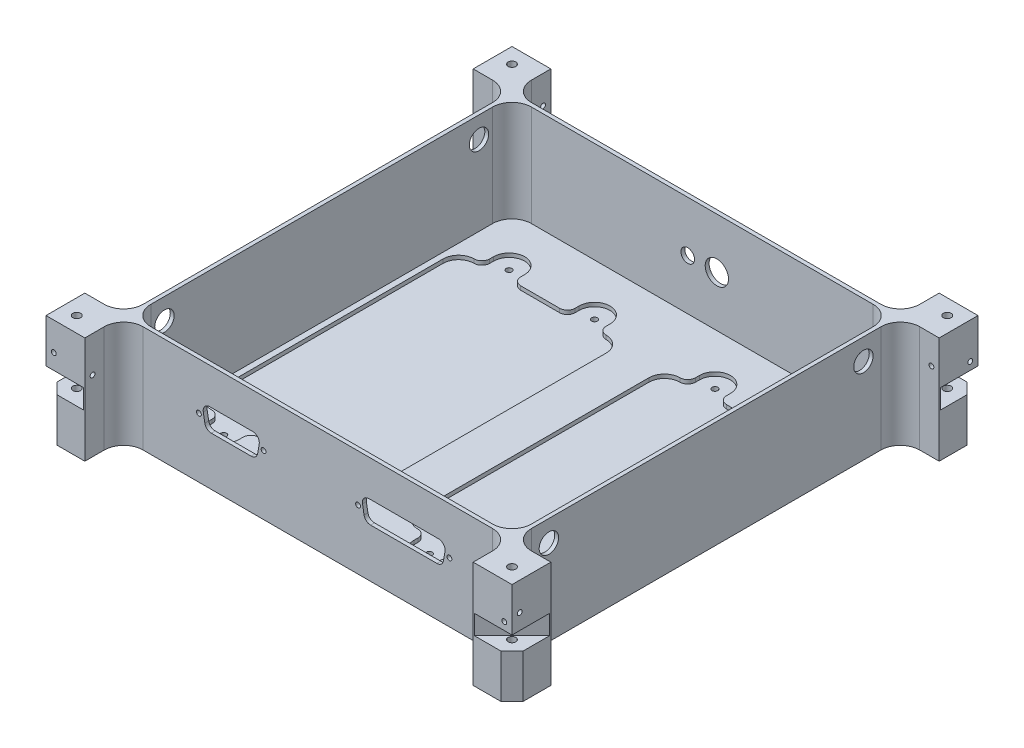
SolidWorks part; units mm, degrees
ref_plane "Front" through (0, 0, 0) normal (0, 0, 1) x (1, 0, 0)
ref_plane "Top" through (0, 0, 0) normal (0, 1, 0) x (1, 0, 0)
ref_plane "Right" through (0, 0, 0) normal (1, 0, 0) x (0, 0, -1)
sketch "Sketch1" plane through (0, 0, 0) normal (0, 1, 0) x (1, 0, 0)
  line L0 (0, 0) -> (0, -42.0956) construction
  line L1 (-120, 120) -> (120, 120)
  line L2 (-120, 120) -> (-120, -120)
  line L3 (-120, -120) -> (120, -120)
  line L4 (120, 120) -> (120, -120)
  line L5 (-120, -120) -> (-100, -120)
  line L6 (-120, -120) -> (-120, -100)
  line L7 (-120, -100) -> (-110, -100)
  line L8 (-100, -120) -> (-100, -110)
  line L9 (-120, 120) -> (-100, 120)
  line L10 (-120, 120) -> (-120, 100)
  line L11 (-120, 100) -> (-110, 100)
  line L12 (-100, 120) -> (-100, 110)
  line L13 (120, 120) -> (100, 120)
  line L14 (120, 120) -> (120, 100)
  line L15 (120, 100) -> (110, 100)
  line L16 (100, 120) -> (100, 110)
  line L17 (110, -100) -> (120, -100)
  line L18 (100, -110) -> (100, -120)
  line L19 (100, -120) -> (120, -120)
  line L20 (120, -100) -> (120, -120)
  line L21 (90, 100) -> (-90, 100)
  line L22 (100, 90) -> (100, -90)
  line L23 (90, -100) -> (-90, -100)
  line L24 (-100, 90) -> (-100, -90)
  line L25 (0, 0) -> (-45.3624, 0) construction
  arc A0 (-90, -100) -> (-100, -110) centre (-90, -110) ccw
  arc A1 (-110, -100) -> (-100, -90) centre (-110, -90) ccw
  arc A2 (110, -100) -> (100, -90) centre (110, -90) cw
  arc A3 (90, -100) -> (100, -110) centre (90, -110) cw
  arc A4 (110, 100) -> (100, 90) centre (110, 90) ccw
  arc A5 (90, 100) -> (100, 110) centre (90, 110) ccw
  arc A6 (-110, 100) -> (-100, 90) centre (-110, 90) cw
  arc A7 (-90, 100) -> (-100, 110) centre (-90, 110) cw
  dimension "D14" = 20
  dimension "D5" = 20
  dimension "D1" = 240
  dimension "D2" = 240
  dimension "D3" = 120
  dimension "D4" = 120
  dimension "D15" = 10
  dimension "D16" = 10
extrude "Boss-Extrude1" add sketch "Sketch1" along normal mid plane 55 contours L21 A7 L12 L1 L2 L11 A6 L24 A1 L7 L3 L8 A0 L23 A3 L18 L4 L17 A2 L22 A4 L15 L16 A5 region at (0, 0, 0)
sketch "Sketch2" plane through (0, 27.5, 0) normal (0, 1, 0) x (1, 0, 0)
  line L0 (90, 100) -> (-90, 100) construction
  line L1 (-88, 98) -> (88, 98)
  line L2 (-98, 88) -> (-98, -88)
  line L3 (-88, -98) -> (88, -98)
  line L4 (98, 88) -> (98, -88)
  line L5 (90, -100) -> (-90, -100) construction
  line L6 (100, 90) -> (100, -90) construction
  line L7 (-100, 90) -> (-100, -90) construction
  arc A0 (-98, -88) -> (-88, -98) centre (-88, -88) ccw
  arc A1 (88, -98) -> (98, -88) centre (88, -88) ccw
  arc A2 (88, 98) -> (98, 88) centre (88, 88) cw
  arc A3 (-88, 98) -> (-98, 88) centre (-88, 88) ccw
  dimension "D5" = 10
  dimension "D1" = 2
  dimension "D2" = 2
  dimension "D3" = 2
  dimension "D4" = 2
extrude "Cut-Extrude1" cut sketch "Sketch2" against normal blind 52
sketch "Sketch3" plane through (0, -24.5, 0) normal (0, 1, 0) x (1, 0, 0)
  line L0 (-98, 88) -> (-98, -88) construction
  line L1 (-95, 67.5) -> (-87, 67.5)
  line L2 (-95, 67.5) -> (-95, -67.5)
  line L3 (-95, -67.5) -> (-87, -67.5)
  line L4 (-11, 67.5) -> (-11, -67.5)
  line L5 (-120, -100) -> (-120, -120) construction
  line L6 (-120, -120) -> (-100, -120) construction
  line L7 (-23, -73.5) -> (-23, -71.5)
  line L8 (-39, -73.5) -> (-39, -71.5)
  line L9 (-67, -73.5) -> (-67, -71.5)
  line L10 (-83, -73.5) -> (-83, -71.5)
  line L11 (-63, -67.5) -> (-43, -67.5)
  line L12 (-19, -67.5) -> (-11, -67.5)
  line L13 (-88, -98) -> (88, -98) construction
  line L14 (0, 0) -> (-67, 0) construction
  line L15 (-19, 67.5) -> (-11, 67.5)
  line L16 (-63, 67.5) -> (-43, 67.5)
  line L17 (-83, 73.5) -> (-83, 71.5)
  line L18 (-67, 73.5) -> (-67, 71.5)
  line L19 (-39, 73.5) -> (-39, 71.5)
  line L20 (-23, 73.5) -> (-23, 71.5)
  line L21 (-95, 67.5) -> (-87, 67.5)
  line L22 (-63, 67.5) -> (-43, 67.5)
  line L23 (-19, 67.5) -> (-11, 67.5)
  line L24 (0, 0) -> (0, 64.5999) construction
  line L25 (19, 67.5) -> (11, 67.5)
  line L26 (19, 67.5) -> (11, 67.5)
  line L27 (63, 67.5) -> (43, 67.5)
  line L28 (95, 67.5) -> (87, 67.5)
  line L29 (23, 73.5) -> (23, 71.5)
  line L30 (39, 73.5) -> (39, 71.5)
  line L31 (67, 73.5) -> (67, 71.5)
  line L32 (83, 73.5) -> (83, 71.5)
  line L33 (63, 67.5) -> (43, 67.5)
  line L34 (19, -67.5) -> (11, -67.5)
  line L35 (63, -67.5) -> (43, -67.5)
  line L36 (83, -73.5) -> (83, -71.5)
  line L37 (67, -73.5) -> (67, -71.5)
  line L38 (39, -73.5) -> (39, -71.5)
  line L39 (23, -73.5) -> (23, -71.5)
  line L40 (11, 67.5) -> (11, -67.5)
  line L41 (95, -67.5) -> (87, -67.5)
  line L42 (95, 67.5) -> (95, -67.5)
  line L43 (95, 67.5) -> (87, 67.5)
  arc A0 (-83, -73.5) -> (-67, -73.5) centre (-75, -73.5) ccw
  arc A1 (-39, -73.5) -> (-23, -73.5) centre (-31, -73.5) ccw
  arc A2 (-83, -71.5) -> (-87, -67.5) centre (-87, -71.5) ccw
  arc A3 (-63, -67.5) -> (-67, -71.5) centre (-63, -71.5) ccw
  arc A4 (-39, -71.5) -> (-43, -67.5) centre (-43, -71.5) ccw
  arc A5 (-19, -67.5) -> (-23, -71.5) centre (-19, -71.5) ccw
  arc A6 (-19, 67.5) -> (-23, 71.5) centre (-19, 71.5) cw
  arc A7 (-39, 71.5) -> (-43, 67.5) centre (-43, 71.5) cw
  arc A8 (-63, 67.5) -> (-67, 71.5) centre (-63, 71.5) cw
  arc A9 (-83, 71.5) -> (-87, 67.5) centre (-87, 71.5) cw
  arc A10 (-39, 73.5) -> (-23, 73.5) centre (-31, 73.5) cw
  arc A11 (-83, 73.5) -> (-67, 73.5) centre (-75, 73.5) cw
  circle A12 centre (-75, 73.5) radius 1.5
  circle A13 centre (-31, 73.5) radius 1.5
  circle A14 centre (-31, -73.5) radius 1.5
  circle A15 centre (-75, -73.5) radius 1.5
  arc A16 (-87, 67.5) -> (-95, 59.5) centre (-87, 59.5) ccw
  arc A17 (-11, 59.5) -> (-19, 67.5) centre (-19, 59.5) ccw
  arc A18 (-19, -67.5) -> (-11, -59.5) centre (-19, -59.5) ccw
  arc A19 (-95, -59.5) -> (-87, -67.5) centre (-87, -59.5) ccw
  arc A20 (95, -59.5) -> (87, -67.5) centre (87, -59.5) cw
  arc A21 (19, -67.5) -> (11, -59.5) centre (19, -59.5) cw
  arc A22 (11, 59.5) -> (19, 67.5) centre (19, 59.5) cw
  arc A23 (87, 67.5) -> (95, 59.5) centre (87, 59.5) cw
  circle A24 centre (75, -73.5) radius 1.5
  circle A25 centre (31, -73.5) radius 1.5
  circle A26 centre (31, 73.5) radius 1.5
  circle A27 centre (75, 73.5) radius 1.5
  arc A28 (83, 73.5) -> (67, 73.5) centre (75, 73.5) ccw
  arc A29 (39, 73.5) -> (23, 73.5) centre (31, 73.5) ccw
  arc A30 (83, 71.5) -> (87, 67.5) centre (87, 71.5) ccw
  arc A31 (63, 67.5) -> (67, 71.5) centre (63, 71.5) ccw
  arc A32 (39, 71.5) -> (43, 67.5) centre (43, 71.5) ccw
  arc A33 (19, 67.5) -> (23, 71.5) centre (19, 71.5) ccw
  arc A34 (19, -67.5) -> (23, -71.5) centre (19, -71.5) cw
  arc A35 (39, -71.5) -> (43, -67.5) centre (43, -71.5) cw
  arc A36 (63, -67.5) -> (67, -71.5) centre (63, -71.5) cw
  arc A37 (83, -71.5) -> (87, -67.5) centre (87, -71.5) cw
  arc A38 (39, -73.5) -> (23, -73.5) centre (31, -73.5) cw
  arc A39 (83, -73.5) -> (67, -73.5) centre (75, -73.5) cw
  dimension "D7" = 16
  dimension "D8" = 16
  dimension "D10" = 8
  dimension "D11" = 8
  dimension "D12" = 8
  dimension "D13" = 4
  dimension "D14" = 4
  dimension "D15" = 8
  dimension "D16" = 4
  dimension "D17" = 4
  dimension "D4" = 3
  dimension "D19" = 3
  dimension "D20" = 3
  dimension "D21" = 3
  dimension "D22" = 16
  dimension "D23" = 16
  dimension "D24" = 16
  dimension "D25" = 8
  dimension "D1" = 84
  dimension "D2" = 135
  dimension "D3" = 3
  dimension "D5" = 45
  dimension "D6" = 89
  dimension "D9" = 46.5
  dimension "D18" = 26.5
extrude "Cut-Extrude2" cut sketch "Sketch3" against normal blind 2 contours L2 A19 A2 L10 A0 L9 A3 L11 A4 L8 A1 L7 A5 A18 L4 A17 A6 L20 A10 L19 A7 L16 A8 L18 A11 L17 A9 A16 A15 A14 A13 A12 | A39 L36 A37 A20 L42 A23 A30 L32 A28 L31 A31 L27 A32 L30 A29 L29 A33 A22 L40 A21 A34 L39 A38 L38 A35 L35 A36 L37 A26 A24 A25 A27 region at (-53, -24.5, 0) region at (53, -24.5, 0)
sketch "Sketch5" plane through (0, -27.5, 0) normal (0, -1, 0) x (1, 0, 0)
  line L0 (90, 100) -> (-90, 100) construction
  line L1 (-88, 98) -> (88, 98)
  line L2 (-98, 88) -> (-98, -88)
  line L3 (-88, -98) -> (88, -98)
  line L4 (98, 88) -> (98, -88)
  line L5 (-100, -90) -> (-100, 90) construction
  line L6 (90, -100) -> (-90, -100) construction
  line L7 (100, -90) -> (100, 90) construction
  arc A3 (-98, -88) -> (-88, -98) centre (-88, -88) ccw
  arc A4 (88, -98) -> (98, -88) centre (88, -88) ccw
  arc A5 (88, 98) -> (98, 88) centre (88, 88) cw
  arc A6 (-88, 98) -> (-98, 88) centre (-88, 88) ccw
  dimension "D5" = 10
  dimension "D1" = 2
  dimension "D2" = 2
  dimension "D3" = 2
  dimension "D4" = 2
extrude "Boss-Extrude2" add sketch "Sketch5" along normal blind 2
extrude "Cut-Extrude3" cut sketch "Sketch3<3>" against normal up to next contours A12 | A13 | A26 | A27 | A15 | A14 | A25 | A24
sketch "Sketch3<3>" plane through (0, -24.5, 0) normal (0, 1, 0) x (1, 0, 0) same geometry as "Sketch3"
sketch "Sketch4" plane through (0, -29.5, 0) normal (0, -1, 0) x (1, 0, 0)
  line L0 (-20.1726, 75.4412) -> (-20.1453, 75.4428)
  line L1 (-88, 98) -> (88, 98)
  line L2 (-98, 88) -> (-98, -88)
  line L3 (-88, -98) -> (88, -98)
  line L4 (98, 88) -> (98, -88)
  line L5 (-100, -90) -> (-100, 90) construction
  line L6 (90, -100) -> (-90, -100) construction
  line L7 (-95, 88) -> (-95, 83.1437)
  line L8 (95, -88) -> (95, -83.1437)
  line L9 (95, 88) -> (95, 83.1437)
  line L10 (20.1453, 75.4428) -> (20.1726, 75.4412)
  line L11 (-58.2668, 70.5) -> (-47.7332, 70.5)
  line L12 (58.2668, -70.5) -> (47.7332, -70.5)
  line L13 (-20.1726, -75.4412) -> (-20.1453, -75.4428)
  line L14 (8, -59.5) -> (8, 59.5)
  line L15 (98, -70.5) -> (98, 70.5)
  line L17 (58.2668, 70.5) -> (47.7332, 70.5)
  line L18 (20.1726, -75.4412) -> (20.1453, -75.4428)
  line L21 (-98, -70.5) -> (-95, -70.5)
  line L22 (-98, -70.5) -> (-98, 70.5)
  line L23 (98, 88) -> (98, -88)
  line L24 (-8, -59.5) -> (-8, 59.5)
  line L25 (-95, -59.5) -> (-95, 59.5) construction
  line L27 (-63, -67.5) -> (-43, -67.5) construction
  line L29 (-58.2668, -70.5) -> (-47.7332, -70.5)
  line L30 (62.7139, 0) -> (-62.7139, 0) construction
  line L31 (0, 0) -> (0, 40.1064) construction
  line L32 (-88, 95) -> (88, 95)
  line L33 (-88, -95) -> (88, -95)
  line L34 (-95, 88) -> (-95, 83.1437)
  line L37 (-95, -88) -> (-95, -83.1437)
  arc A0 (-84.0588, -79.74) -> (-64.1726, -75.4412) centre (-75, -73.5) ccw
  arc A1 (-88, 98) -> (-98, 88) centre (-88, 88) ccw
  arc A2 (88, 98) -> (98, 88) centre (88, 88) cw
  arc A3 (88, -98) -> (98, -88) centre (88, -88) ccw
  arc A4 (-98, -88) -> (-88, -98) centre (-88, -88) ccw
  arc A5 (-15.8654, -70.0439) -> (-20.1453, -75.4428) centre (-14.1556, -75.7952) ccw
  arc A6 (84.0588, -79.74) -> (95, -83.1437) centre (89, -83.1437) cw
  arc A7 (-41.8274, 75.4412) -> (-47.7332, 70.5) centre (-47.7332, 76.5) cw
  arc A8 (-58.2668, 70.5) -> (-64.1726, 75.4412) centre (-58.2668, 76.5) cw
  arc A9 (-41.8274, 75.4412) -> (-20.1726, 75.4412) centre (-31, 73.5) cw
  arc A10 (-84.0588, 79.74) -> (-64.1726, 75.4412) centre (-75, 73.5) cw
  arc A11 (20.1453, -75.4428) -> (15.8654, -70.0439) centre (14.1556, -75.7952) ccw
  arc A12 (84.0588, 79.74) -> (95, 83.1437) centre (89, 83.1437) ccw
  arc A13 (41.8274, -75.4412) -> (47.7332, -70.5) centre (47.7332, -76.5) cw
  arc A14 (58.2668, -70.5) -> (64.1726, -75.4412) centre (58.2668, -76.5) cw
  arc A15 (41.8274, -75.4412) -> (20.1726, -75.4412) centre (31, -73.5) cw
  arc A16 (84.0588, 79.74) -> (64.1726, 75.4412) centre (75, 73.5) ccw
  arc A17 (41.8274, 75.4412) -> (20.1726, 75.4412) centre (31, 73.5) ccw
  arc A18 (58.2668, 70.5) -> (64.1726, 75.4412) centre (58.2668, 76.5) ccw
  arc A19 (41.8274, 75.4412) -> (47.7332, 70.5) centre (47.7332, 76.5) ccw
  arc A20 (15.8654, 70.0439) -> (20.1453, 75.4428) centre (14.1556, 75.7952) ccw
  arc A21 (-41.8274, -75.4412) -> (-20.1726, -75.4412) centre (-31, -73.5) ccw
  arc A22 (-58.2668, -70.5) -> (-64.1726, -75.4412) centre (-58.2668, -76.5) ccw
  arc A23 (-41.8274, -75.4412) -> (-47.7332, -70.5) centre (-47.7332, -76.5) ccw
  arc A24 (-84.0588, -79.74) -> (-95, -83.1437) centre (-89, -83.1437) ccw
  arc A25 (-20.1453, 75.4428) -> (-15.8654, 70.0439) centre (-14.1556, 75.7952) ccw
  arc A27 (98, -88) -> (88, -98) centre (88, -88) cw
  arc A28 (84.0588, -79.74) -> (64.1726, -75.4412) centre (75, -73.5) cw
  arc A29 (88, 95) -> (95, 88) centre (88, 88) cw
  arc A30 (-88, 95) -> (-95, 88) centre (-88, 88) ccw
  arc A31 (-95, -88) -> (-88, -95) centre (-88, -88) ccw
  arc A32 (88, -95) -> (95, -88) centre (88, -88) ccw
  arc A33 (-84.0588, 79.74) -> (-95, 83.1437) centre (-89, 83.1437) cw
  arc A49 (-8, 59.5) -> (-19, 70.5) centre (-19, 59.5) ccw
  arc A50 (-8, 59.5) -> (-15.8654, 70.0439) centre (-19, 59.5) ccw
  arc A52 (19, 70.5) -> (8, 59.5) centre (19, 59.5) ccw
  arc A53 (15.8654, 70.0439) -> (8, 59.5) centre (19, 59.5) ccw
  arc A55 (-19, -70.5) -> (-8, -59.5) centre (-19, -59.5) ccw
  arc A56 (-15.8654, -70.0439) -> (-8, -59.5) centre (-19, -59.5) ccw
  arc A58 (8, -59.5) -> (19, -70.5) centre (19, -59.5) ccw
  arc A59 (8, -59.5) -> (15.8654, -70.0439) centre (19, -59.5) ccw
  dimension "D5" = 10
  dimension "D10" = 22
  dimension "D11" = 22
  dimension "D12" = 12
  dimension "D13" = 12
  dimension "D14" = 90
  dimension "D15" = 12
  dimension "D8" = 12
  dimension "D16" = 3
  dimension "D20" = 12
  dimension "D6" = 12
  dimension "D21" = 12
  dimension "D2" = 2
  dimension "D3" = 2
  dimension "D4" = 3
  dimension "D7" = 3
  dimension "D9" = 3
  dimension "D17" = 3
  dimension "D18" = 3
  dimension "D19" = 3
extrude "Cut-Extrude4" cut sketch "Sketch4" against normal blind 2 contours A59 L14 A53 A20 L10 A17 A19 L17 A18 A16 A12 L9 A29 L32 A30 L7 A33 A10 A8 L11 A7 A9 L0 A25 A50 L24 A56 A5 L13 A21 A23 L29 A22 A0 A24 L37 A31 L33 A32 L8 A6 A28 A14 L12 A13 A15 L18 A11 region at (0, -29.5, 0)
sketch "Sketch6" plane through (0, -24.5, 0) normal (0, 1, 0) x (1, 0, 0)
  line L0 (-120, -120) -> (-100, -120) construction
  line L1 (100, -120) -> (120, -120) construction
  line L2 (-120, -100) -> (-120, -120) construction
  line L3 (120, -100) -> (120, -120) construction
  point P0 (-88, -81)
  point P1 (0, -81)
  point P2 (88, -81)
  dimension "D1" = 39
  dimension "D2" = 39
  dimension "D3" = 39
  dimension "D4" = 32
  dimension "D5" = 32
  dimension "D6" = 0
hole_wizard "Ø3.0 (3) Diameter Hole1" positions "Sketch8" profile "Sketch7" hole size "Ø3.0" standard "AS" end condition up to next
sketch "Sketch8" plane through (0, -24.5, 0) normal (0, 1, 0) x (1, 0, 0)
  point P0 (-88, -81)
  point P3 (0, -81)
  point P6 (88, -81)
sketch "Sketch7" plane through (-88, -24.5, 81) normal (1, 0, 0) x (0, 0, 1)
  line L0 (0, 0) -> (0, 3)
  line L1 (0, 3) -> (1.5, 3)
  line L2 (1.5, 3) -> (1.5, 0)
  line L5 (1.5, 0) -> (0, 0)
  line L11 (0, -6.35) -> (0, 107.95) construction
  dimension "Thru Hole Dia." = 3
  dimension "Thru Hole Depth" = 3
sketch "Sketch9" plane through (100, 0, 0) normal (1, 0, 0) x (0, 0, -1)
  line L0 (0, 0) -> (-20.7242, 0) construction
  line L1 (0, 0) -> (0, 15.0037) construction
  line L3 (-120, 27.5) -> (-120, -27.5) construction
  line L4 (-100, 27.5) -> (-120, 27.5) construction
  line L5 (90, 27.5) -> (-90, 27.5) construction
  point P0 (-81, 16.5)
  point P1 (-116, 13)
  point P10 (81, 16.5)
  point P11 (116, 13)
  dimension "D1" = 11
  dimension "D2" = 81
  dimension "D3" = 4
  dimension "D4" = 14.5
hole_wizard "Ø10.0 (10) Diameter Hole1" positions "Sketch14" profile "Sketch15" hole size "Ø10.0" standard "AS" end condition through all
sketch "Sketch14" plane through (100, 0, 0) normal (1, 0, 0) x (0, 0, -1)
  point P0 (-81, 16.5)
  point P3 (81, 16.5)
sketch "Sketch15" plane through (100, 16.5, 81) normal (0, 1, 0) x (0, 0, -1)
  line L0 (0, 0) -> (0, 220)
  line L1 (0, 220) -> (5, 220)
  line L2 (5, 220) -> (5, 0)
  line L5 (5, 0) -> (0, 0)
  line L11 (0, -6.35) -> (0, 107.95) construction
  dimension "Thru Hole Dia." = 10
  dimension "Thru Hole Depth" = 220
sketch "Sketch16" plane through (0, -27.5, 0) normal (0, -1, 0) x (1, 0, 0)
  line L0 (-120, -100.6111) -> (-100.6111, -120)
  line L1 (-120, -120) -> (-120, -100) construction
  line L2 (-120, -120) -> (-100, -120) construction
  line L3 (-100, -120) -> (-120, -100)
  line L4 (-120, -114.3431) -> (-114.3431, -120)
  line L5 (-120, -114.3431) -> (-120, -120)
  line L6 (-120, -120) -> (-114.3431, -120)
  line M25 (-120, -100) -> (-120, -120)
  line M26 (-120, -120) -> (-100, -120)
  dimension "D1" = 13.71
  dimension "D2" = 4
extrude "Cut-Extrude5" cut sketch "Sketch16" against normal blind 22.5 contours L4 M25 M26 region at (-118.1144, -27.5, -118.1144)
ref_axis "Axis1" through (0, 0, 0) along (0, 1, 0)
pattern_circular "CirPattern1" count 4 over 360 about axis through (0, 0, 0) along (0, 1, 0) of "Cut-Extrude5"
ref_plane "Plane1" through (0, -5, 0) normal (0, -1, 0) x (-1, 0, 0)
sketch "Sketch17" plane through (0, -5, 0) normal (0, -1, 0) x (-1, 0, 0)
  line L0 (-114.3431, 120) -> (-120, 120)
  line L1 (-120, 120) -> (-120, 114.3431)
  line L2 (-120, 100.6111) -> (-100.6111, 120)
  line L3 (-120, 114.3431) -> (-120, 100) construction
  line L4 (-100, 120) -> (-114.3431, 120) construction
  line L5 (-120, 100) -> (-110, 100) construction
  line L6 (-120, 114.3431) -> (-120, 100.6111)
  line L7 (-114.3431, 120) -> (-100.6111, 120)
  dimension "D1" = 13.71
  dimension "D2" = 45
extrude "Cut-Extrude6" cut sketch "Sketch17" against normal blind 10
pattern_circular "CirPattern2" count 4 over 360 about axis through (0, 0, 0) along (0, 1, 0) of "Cut-Extrude6"
sketch "Sketch18" plane through (0, 0, -100) normal (0, 0, -1) x (-1, 0, 0)
  line L0 (-23.4875, 0) -> (26.2507, 0) construction
  line L1 (0, 0) -> (0, 15.8284) construction
  circle A0 centre (-7.5, 1.5) radius 6
  circle A1 centre (7.5, 1.5) radius 3.5
  dimension "D5" = 12
  dimension "D6" = 7
  dimension "D1" = 7.5
  dimension "D2" = 7.5
  dimension "D3" = 1.5
  dimension "D4" = 1.5
extrude "Cut-Extrude7" cut sketch "Sketch18" against normal up to next
sketch "Sketch19" plane through (0, 0, -120) normal (0, 0, -1) x (-1, 0, 0)
  line L0 (-120, 27.5) -> (-120, 5) construction
  line L2 (-100, 27.5) -> (-120, 27.5) construction
  line L3 (120, 27.5) -> (120, 5) construction
  line L4 (120, 27.5) -> (100, 27.5) construction
  point P0 (-116, 13)
  point P1 (116, 13)
  dimension "D1" = 4
  dimension "D2" = 14.5
  dimension "D3" = 4
  dimension "D4" = 14.5
sketch "Sketch22" plane through (0, 27.5, 0) normal (0, 1, 0) x (1, 0, 0)
  line L0 (-120, 100.6111) -> (-100.6111, 120)
  line L1 (-120, 120) -> (-120, 100) construction
  line L2 (-120, 120) -> (-100, 120) construction
  line L3 (-120, 100) -> (-110, 100) construction
  line L4 (0, 0) -> (-112.0764, 112.0764) construction
  line L5 (0, 0) -> (48.7369, 0) construction
  circle A0 centre (-112.0764, 112.0764) radius 2
  dimension "D4" = 4
  dimension "D1" = 13.71
  dimension "D2" = 45
  dimension "D3" = 158.5
  dimension "D5" = 135
extrude "Cut-Extrude8" cut sketch "Sketch22" against normal through all contours A0 region at (-112.0764, 27.5, -112.0764)
pattern_circular "CirPattern3" count 4 every 90 about axis through (0, 0, 0) along (0, 1, 0) of "Cut-Extrude8"
hole_wizard "M3x0.5 Tapped Hole1" positions "Sketch24" profile "Sketch23" tap size "M3x0.5" standard "ANSI Metric"
sketch "Sketch24" plane through (-120, 0, 0) normal (-1, 0, 0) x (0, 0, 1)
  line L0 (100, 27.5) -> (120, 27.5) construction
  line L1 (120, 27.5) -> (120, 5) construction
  line L2 (-120, 27.5) -> (-100, 27.5) construction
  line L3 (-120, 27.5) -> (-120, 5) construction
  point P0 (-116, 13)
  point P2 (116, 9)
  dimension "D1" = 18.5
  dimension "D2" = 4
  dimension "D3" = 14.5
  dimension "D4" = 4
sketch "Sketch23" plane through (-120, 13, -116) normal (0, 1, 0) x (0, 0, 1)
  line L0 (0, 0) -> (0, 20.7511)
  line L1 (0, 20.7511) -> (1.25, 20)
  line L2 (1.25, 20) -> (1.25, 0)
  line L5 (1.25, 0) -> (0, 0)
  line L10 (0, 20.7511) -> (-1.25, 20) construction
  line L11 (0, -6.35) -> (0, 107.95) construction
  dimension "Tap Drill Dia." = 2.5
  dimension "Tap Drill Depth" = 20
  dimension "Drill Angle" = 118
cosmetic thread "Hole Thread1" parameters "D1"=20, "D2"=4
cosmetic thread "Hole Thread2" parameters "D1"=20, "D2"=4
hole_wizard "M3x0.5 Tapped Hole2" positions "Sketch26" profile "Sketch25" tap size "M3x0.5" standard "ANSI Metric"
sketch "Sketch26" plane through (0, 0, 120) normal (0, 0, 1) x (1, 0, 0)
  line L0 (-120, 27.5) -> (-100, 27.5) construction
  line L1 (-120, 27.5) -> (-120, 5) construction
  line L2 (100, 27.5) -> (120, 27.5) construction
  line L4 (120, 27.5) -> (120, 5) construction
  point P0 (-116, 13)
  point P2 (116, 9)
  dimension "D1" = 14.5
  dimension "D2" = 4
  dimension "D3" = 18.5
  dimension "D4" = 4
sketch "Sketch25" plane through (-116, 13, 120) normal (1, 0, 0) x (0, -1, 0)
  line L0 (0, 0) -> (0, 22.2511)
  line L1 (0, 22.2511) -> (1.25, 21.5)
  line L2 (1.25, 21.5) -> (1.25, 0)
  line L5 (1.25, 0) -> (0, 0)
  line L10 (0, 22.2511) -> (-1.25, 21.5) construction
  line L11 (0, -6.35) -> (0, 107.95) construction
  dimension "Tap Drill Dia." = 2.5
  dimension "Tap Drill Depth" = 21.5
  dimension "Drill Angle" = 118
cosmetic thread "Hole Thread3" parameters "D1"=20, "D2"=3
cosmetic thread "Hole Thread4" parameters "D1"=20, "D2"=3
hole_wizard "M3x0.5 Tapped Hole3" positions "Sketch28" profile "Sketch27" tap size "M3x0.5" standard "ANSI Metric"
sketch "Sketch28" plane through (120, 0, 0) normal (1, 0, 0) x (0, 0, -1)
  line L0 (-100, 27.5) -> (-120, 27.5) construction
  line L1 (-120, 27.5) -> (-120, 5) construction
  line L2 (120, 27.5) -> (100, 27.5) construction
  line L3 (120, 27.5) -> (120, 5) construction
  point P0 (-116, 13)
  point P2 (116, 9)
  dimension "D1" = 14.5
  dimension "D2" = 4
  dimension "D3" = 18.5
  dimension "D4" = 4
sketch "Sketch27" plane through (120, 13, 116) normal (0, 1, 0) x (0, 0, -1)
  line L0 (0, 0) -> (0, 22.2511)
  line L1 (0, 22.2511) -> (1.25, 21.5)
  line L2 (1.25, 21.5) -> (1.25, 0)
  line L5 (1.25, 0) -> (0, 0)
  line L10 (0, 22.2511) -> (-1.25, 21.5) construction
  line L11 (0, -6.35) -> (0, 107.95) construction
  dimension "Tap Drill Dia." = 2.5
  dimension "Tap Drill Depth" = 21.5
  dimension "Drill Angle" = 118
cosmetic thread "Hole Thread5" parameters "D1"=20, "D2"=3
cosmetic thread "Hole Thread6" parameters "D1"=20, "D2"=3
hole_wizard "M3x0.5 Tapped Hole4" positions "Sketch30" profile "Sketch29" tap size "M3x0.5" standard "ANSI Metric"
sketch "Sketch30" plane through (0, 0, -120) normal (0, 0, -1) x (-1, 0, 0)
  line L0 (120, 27.5) -> (120, 5) construction
  line L1 (120, 27.5) -> (100, 27.5) construction
  line L2 (-120, 27.5) -> (-120, 5) construction
  line L3 (-100, 27.5) -> (-120, 27.5) construction
  point P0 (-116, 13)
  point P2 (116, 9)
  dimension "D1" = 4
  dimension "D2" = 18.5
  dimension "D3" = 4
  dimension "D4" = 14.5
sketch "Sketch29" plane through (116, 13, -120) normal (1, 0, 0) x (0, 1, 0)
  line L0 (0, 0) -> (0, 22.2511)
  line L1 (0, 22.2511) -> (1.25, 21.5)
  line L2 (1.25, 21.5) -> (1.25, 0)
  line L5 (1.25, 0) -> (0, 0)
  line L10 (0, 22.2511) -> (-1.25, 21.5) construction
  line L11 (0, -6.35) -> (0, 107.95) construction
  dimension "Tap Drill Dia." = 2.5
  dimension "Tap Drill Depth" = 21.5
  dimension "Drill Angle" = 118
cosmetic thread "Hole Thread7" parameters "D1"=20, "D2"=3
cosmetic thread "Hole Thread8" parameters "D1"=20, "D2"=3
sketch "Sketch31" plane through (0, 0, 100) normal (0, 0, 1) x (1, 0, 0)
  line L0 (-55.6517, 9) -> (-33.5483, 9)
  line L1 (-59, 5.0096) -> (-58.1889, 0.4096)
  line L2 (-30.2, 5.0096) -> (-31.0111, 0.4096)
  line L3 (-34.3595, -2.4) -> (-54.8405, -2.4)
  line L4 (90, 27.5) -> (-90, 27.5) construction
  line L6 (26.3483, 9) -> (62.1517, 9)
  line L7 (65.5, 5.0096) -> (64.6889, 0.4096)
  line L8 (61.3405, -2.4) -> (27.1595, -2.4)
  line L9 (23.8111, 0.4096) -> (23, 5.0096)
  line L12 (120, 27.5) -> (120, 5) construction
  line L13 (-120, 27.5) -> (-120, 5) construction
  arc A0 (-33.5483, 9) -> (-30.2, 5.0096) centre (-33.5483, 5.6) cw
  arc A1 (-55.6517, 9) -> (-59, 5.0096) centre (-55.6517, 5.6) ccw
  arc A2 (-31.0111, 0.4096) -> (-34.3595, -2.4) centre (-34.3595, 1) cw
  arc A3 (-58.1889, 0.4096) -> (-54.8405, -2.4) centre (-54.8405, 1) ccw
  arc A4 (62.1517, 9) -> (65.5, 5.0096) centre (62.1517, 5.6) cw
  arc A5 (64.6889, 0.4096) -> (61.3405, -2.4) centre (61.3405, 1) cw
  arc A6 (27.1595, -2.4) -> (23.8111, 0.4096) centre (27.1595, 1) cw
  arc A7 (23, 5.0096) -> (26.3483, 9) centre (26.3483, 5.6) cw
  dimension "D1" = 3.4
  dimension "D2" = 3.4
  dimension "D3" = 3.4
  dimension "D4" = 3.4
  dimension "D11" = 3.4
  dimension "D12" = 3.4
  dimension "D13" = 3.4
  dimension "D14" = 3.4
  dimension "D19" = 61
  dimension "D5" = 11.4
  dimension "D6" = 28.8
  dimension "D7" = 80
  dimension "D8" = 80
  dimension "D9" = 18.5
  dimension "D10" = 54.5
  dimension "D15" = 42.5
  dimension "D16" = 11.4
  dimension "D17" = 80
  dimension "D18" = 80
extrude "Cut-Extrude9" cut sketch "Sketch31" against normal blind 10
hole_wizard "M3x0.5 Tapped Hole5" positions "Sketch33" profile "Sketch32" tap size "M3x0.5" standard "ANSI Metric"
sketch "Sketch33" plane through (0, 0, 100) normal (0, 0, 1) x (1, 0, 0)
  line L0 (-54.8405, -2.4) -> (-34.3595, -2.4) construction
  line L2 (62.1517, 9) -> (26.3483, 9) construction
  arc A0 (-55.6517, 9) -> (-59, 5.0096) centre (-55.6517, 5.6) ccw construction
  arc A2 (-30.2, 5.0096) -> (-33.5483, 9) centre (-33.5483, 5.6) ccw construction
  arc A3 (26.3483, 9) -> (23, 5.0096) centre (26.3483, 5.6) ccw construction
  arc A5 (65.5, 5.0096) -> (62.1517, 9) centre (62.1517, 5.6) ccw construction
  point P0 (-61.2517, 3.3)
  point P2 (-27.9517, 3.3)
  point P4 (20.7283, 3.3)
  point P6 (67.7683, 3.3)
  dimension "D1" = 33.3
  dimension "D2" = 5.7
  dimension "D3" = 5.6
  dimension "D4" = 5.5967
  dimension "D5" = 47.04
  dimension "D6" = 5.7
  dimension "D7" = 5.62
  dimension "D8" = 5.6167
sketch "Sketch32" plane through (-61.2517, 3.3, 100) normal (1, 0, 0) x (0, -1, 0)
  line L0 (0, 0) -> (0, 4.7511)
  line L1 (0, 4.7511) -> (1.25, 4)
  line L2 (1.25, 4) -> (1.25, 0)
  line L5 (1.25, 0) -> (0, 0)
  line L10 (0, 4.7511) -> (-1.25, 4) construction
  line L11 (0, -6.35) -> (0, 107.95) construction
  dimension "Tap Drill Dia." = 2.5
  dimension "Tap Drill Depth" = 4
  dimension "Drill Angle" = 118
cosmetic thread "Hole Thread9" parameters "D1"=2, "D2"=3
cosmetic thread "Hole Thread10" parameters "D1"=2, "D2"=3
cosmetic thread "Hole Thread11" parameters "D1"=2, "D2"=3
cosmetic thread "Hole Thread12" parameters "D1"=2, "D2"=3
